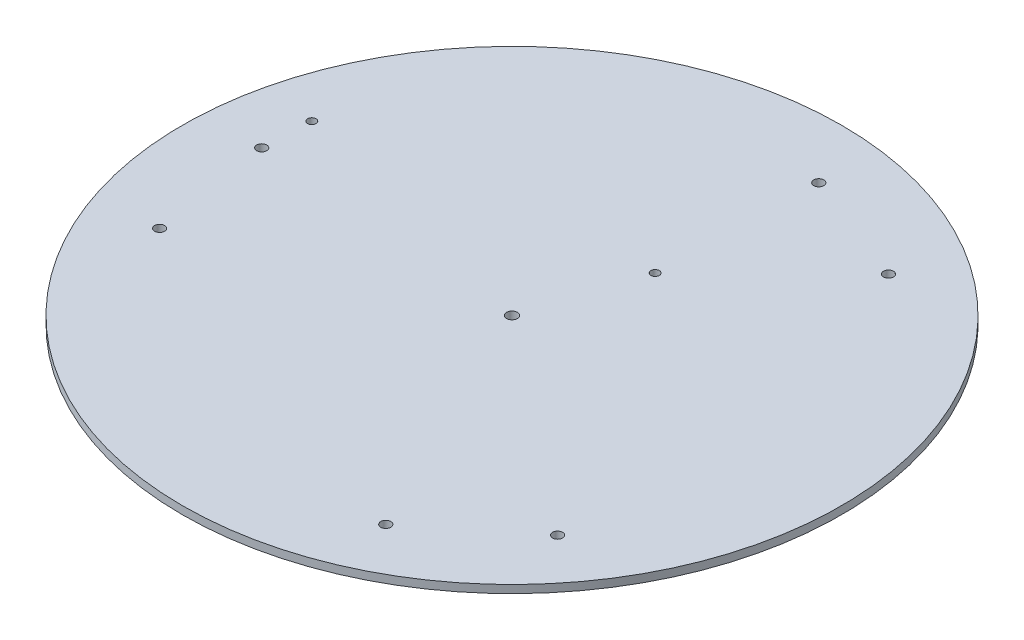
SolidWorks part; units mm, degrees
ref_plane "Front Plane" through (0, 0, 0) normal (0, 0, 1) x (1, 0, 0)
ref_plane "Top Plane" through (0, 0, 0) normal (0, 1, 0) x (1, 0, 0)
ref_plane "Right Plane" through (0, 0, 0) normal (1, 0, 0) x (0, 0, -1)
sketch "Sketch2" plane through (0, 0, 0) normal (0, 1, 0) x (1, 0, 0)
  circle A0 centre (0, 0) radius 125
  dimension "D1" = 250
extrude "Boss-Extrude1" add sketch "Sketch2" along normal blind 3
sketch "Sketch3" plane through (0, 3, 0) normal (0, 1, 0) x (1, 0, 0)
  line L4 (74.6446, 100.2656) -> (65.4599, 76.5843) construction
  line L5 (0, 0) -> (43.5629, 112.3204) construction
  line L6 (74.6446, 100.2656) -> (12.4813, 124.3753) construction
  line L7 (12.4813, 124.3753) -> (3.2966, 100.6941) construction
  line L8 (65.4599, 76.5843) -> (3.2966, 100.6941) construction
  circle A0 centre (0, 0) radius 125 construction
  circle A7 centre (57.8244, 84.9944) radius 1.905
  circle A8 centre (14.6061, 101.7564) radius 1.905
  circle A9 centre (44.6952, -92.5746) radius 1.905
  circle A10 centre (80.8206, -63.5274) radius 1.905
  circle A11 centre (-102.5195, 7.5802) radius 1.905
  circle A12 centre (-95.4267, -38.229) radius 1.905
  point P22 (0, 0)
  point P23 (0.4661, 0.2121)
  dimension "D2" = 3.81
  dimension "D1" = 25.4
  dimension "D3" = 5.08
  dimension "D5" = 66.675
  dimension "D6" = 3
  dimension "D4" = 10.16
extrude "Cut-Extrude1" cut sketch "Sketch3" against normal blind 26 and the other way blind 62
sketch "Sketch4" plane through (0, 3, 0) normal (0, 1, 0) x (1, 0, 0)
  circle A0 centre (0, 0) radius 2.05
  dimension "D1" = 4.1
extrude "Cut-Extrude2" cut sketch "Sketch4" against normal blind 33 and the other way blind 55
sketch "Sketch5" plane through (0, 0, 0) normal (0, -1, 0) x (1, 0, 0)
  circle A0 centre (-101.7781, -25.8548) radius 1.6
  circle A1 centre (13.2168, -41.0922) radius 1.6
  dimension "D1" = 3.2
  dimension "D2" = 3.2
extrude "Cut-Extrude3" cut sketch "Sketch5" against normal through all
